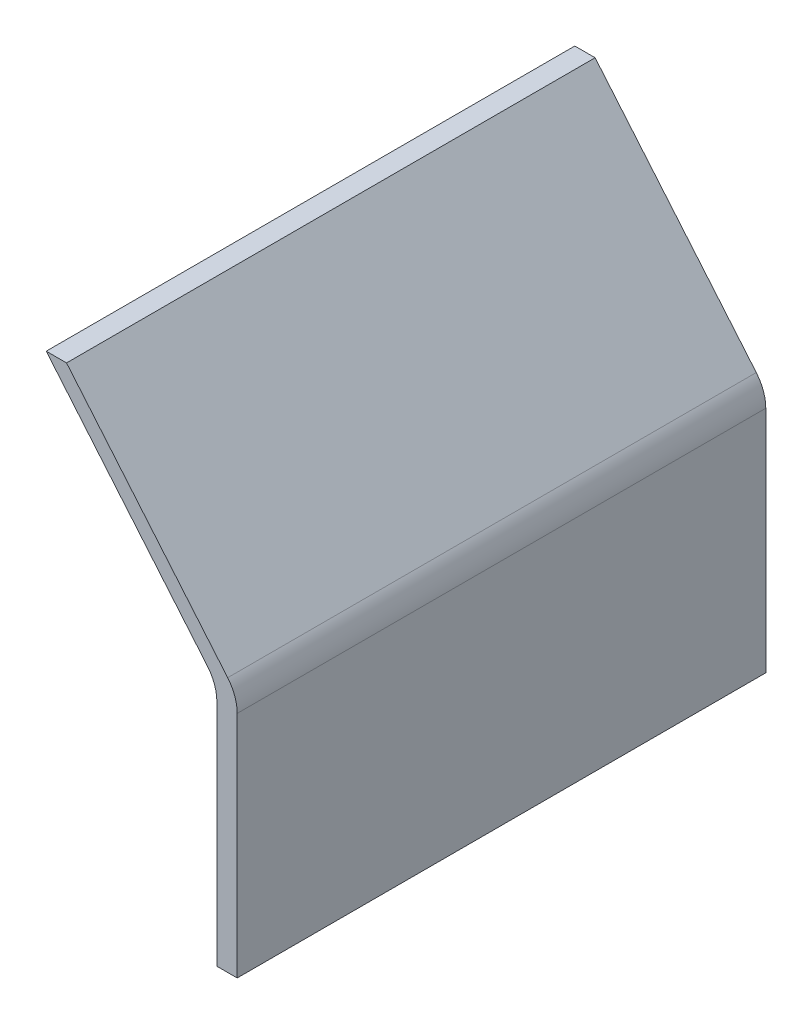
SolidWorks part; units mm, degrees
material "201 Annealed Stainless Steel (SS)"
ref_plane "Front Plane" through (0, 0, 0) normal (0, 0, 1) x (1, 0, 0)
ref_plane "Top Plane" through (0, 0, 0) normal (0, 1, 0) x (1, 0, 0)
ref_plane "Right Plane" through (0, 0, 0) normal (1, 0, 0) x (0, 0, -1)
sketch "Sketch1" plane through (0, 0, 0) normal (0, 0, 1) x (1, 0, 0)
  line L0 (0, 0) -> (-5, 0)
  line L1 (-5, 0) -> (-5, 60)
  line L2 (-5, 60) -> (-46.974, 110.0227)
  line L3 (-46.974, 110.0227) -> (-41.974, 110.0227)
  line L4 (-41.974, 110.0227) -> (0, 60)
  line L5 (0, 60) -> (0, 0)
  dimension "D1" = 5
  dimension "D2" = 5
  dimension "D3" = 60
  dimension "D4" = 140
  dimension "D5" = 65.3
extrude "Funnel - Left Side" add sketch "Sketch1" along normal blind 130
fillet "Fillet1" radius 10 2 edges at (0, 60, 65) (-5, 60, 65)
